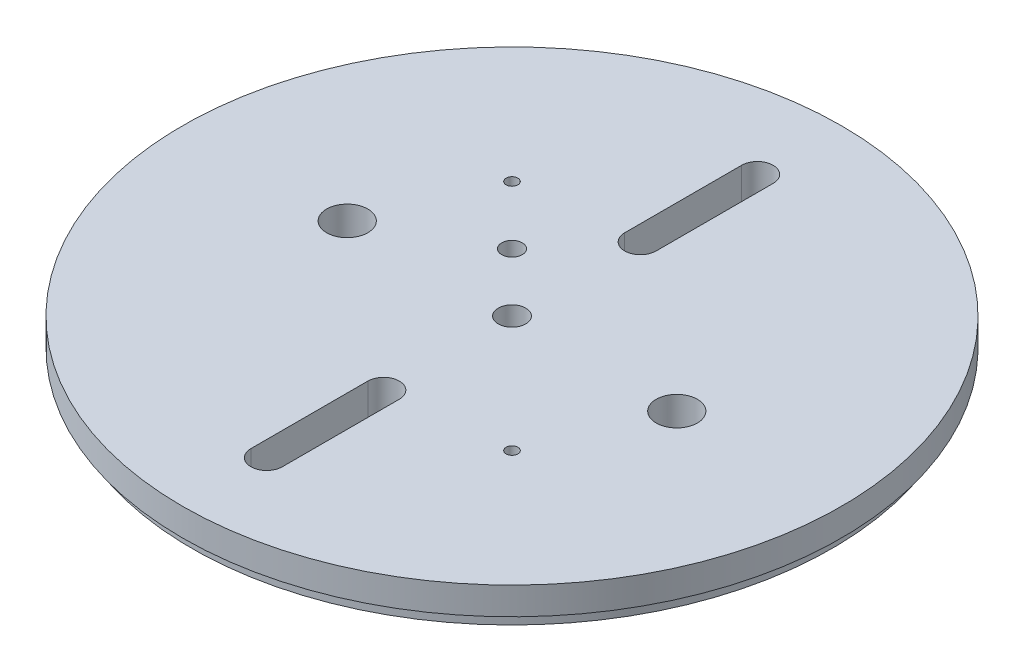
SolidWorks part; units mm, degrees
ref_plane "Front Plane" through (0, 0, 0) normal (0, 0, 1) x (1, 0, 0)
ref_plane "Top Plane" through (0, 0, 0) normal (0, 1, 0) x (1, 0, 0)
ref_plane "Right Plane" through (0, 0, 0) normal (1, 0, 0) x (0, 0, -1)
sketch "Sketch1" plane through (0, 0, 0) normal (0, 1, 0) x (1, 0, 0)
  line L0 (0, -76.2) -> (0, 76.2) construction
  line L1 (-76.2, 0) -> (76.2, 0) construction
  line L2 (-26.9408, 26.9408) -> (0, 0) construction
  line L3 (0, 56.7387) -> (0, 29.6936) construction
  line L4 (3.6407, 56.7387) -> (3.6407, 29.6936)
  line L5 (-3.6407, 56.7387) -> (-3.6407, 29.6936)
  line L6 (0, -56.7387) -> (0, -29.6936) construction
  line L7 (3.6407, -56.7387) -> (3.6407, -29.6936)
  line L8 (-3.6407, -56.7387) -> (-3.6407, -29.6936)
  line L9 (-53.8815, -53.8815) -> (54.3236, 54.3236) construction
  circle A0 centre (0, 0) radius 76.2
  circle A1 centre (0, 0) radius 3.175
  circle A2 centre (38.1, 0) radius 4.7625
  circle A3 centre (-38.1, 0) radius 4.7625
  circle A4 centre (-26.9408, 26.9408) radius 1.3589
  arc A6 (3.6407, 56.7387) -> (-3.6407, 56.7387) centre (0, 56.7387) ccw
  arc A7 (-3.6407, 29.6936) -> (3.6407, 29.6936) centre (0, 29.6936) ccw
  arc A8 (3.6407, -56.7387) -> (-3.6407, -56.7387) centre (0, -56.7387) cw
  arc A9 (-3.6407, -29.6936) -> (3.6407, -29.6936) centre (0, -29.6936) cw
  circle A10 centre (26.9408, -26.9408) radius 1.3589
  circle A11 centre (-13.4704, 13.4704) radius 2.3813
  point P16 (0, 43.2162)
  point P19 (0, 0)
  point P26 (0, -43.2162)
  dimension "D1" = 152.4
  dimension "D2" = 6.35
  dimension "D3" = 9.525
  dimension "D5" = 2.7178
  dimension "D8" = 4.7625
  dimension "D4" = 45
  dimension "D6" = 38.1
  dimension "D7" = 45
extrude "Boss-Extrude1" add sketch "Sketch1" along normal blind 9.525
sketch "Sketch2" plane through (0, 0, 0) normal (0, -1, 0) x (1, 0, 0)
  circle A0 centre (0, 0) radius 76.2
  circle A1 centre (0, 0) radius 74.041
  dimension "D1" = 152.4
  dimension "D2" = 148.082
extrude "Cut-Extrude1" cut sketch "Sketch2" against normal blind 3.175
equation "\"leadDist\"=1.5"
